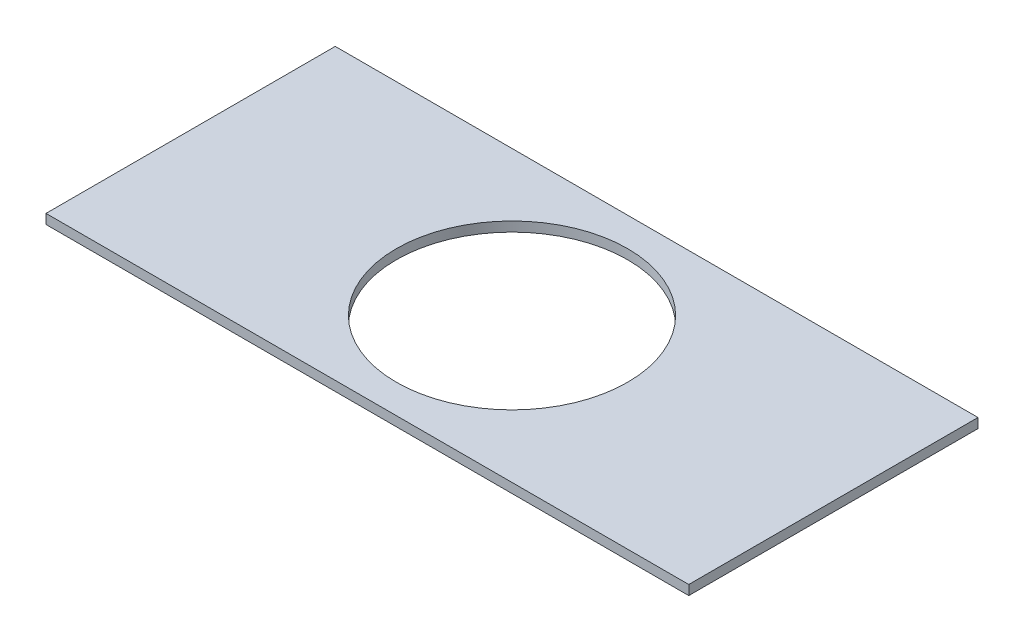
SolidWorks part; units mm, degrees
ref_plane "Front Plane" through (0, 0, 0) normal (0, 0, 1) x (1, 0, 0)
ref_plane "Top Plane" through (0, 0, 0) normal (0, 1, 0) x (1, 0, 0)
ref_plane "Right Plane" through (0, 0, 0) normal (1, 0, 0) x (0, 0, -1)
sketch "Sketch1" plane through (0, 0, 0) normal (0, 1, 0) x (1, 0, 0)
  line L1 (0, 0) -> (200, 0)
  line L2 (0, 0) -> (0, 90)
  line L3 (0, 90) -> (200, 90)
  line L4 (200, 0) -> (200, 90)
  circle A0 centre (100, 45) radius 36
extrude "Boss-Extrude1" add sketch "Sketch1" along normal blind 3
